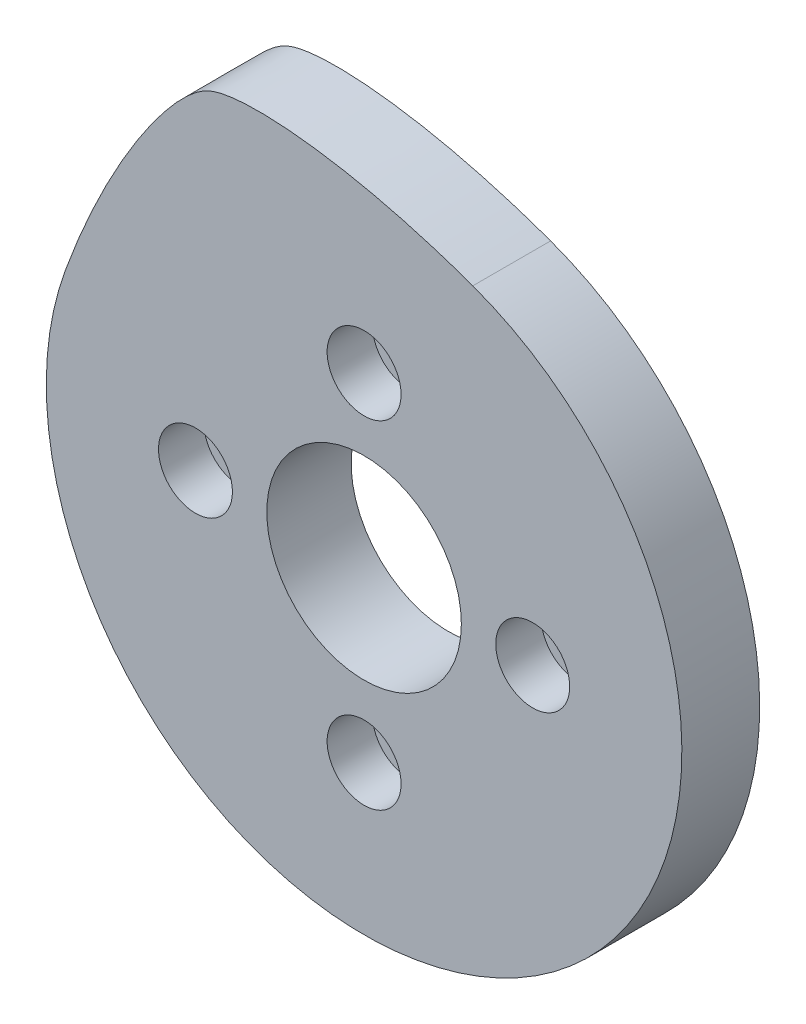
SolidWorks part; units mm, degrees
ref_plane "Front Plane" through (0, 0, 0) normal (1, 0, 0) x (0, 1, 0)
ref_plane "Top Plane" through (0, 0, 0) normal (0, 0, 1) x (0, 1, 0)
ref_plane "Right Plane" through (0, 0, 0) normal (0, 1, 0) x (-1, 0, 0)
sketch "Sketch1" plane through (0, 0, 0) normal (0, 0, 1) x (0, 1, 0)
  circle A0 centre (0, 0) radius 21
  circle A1 centre (0, 0) radius 13 construction
  circle A2 centre (0, 13) radius 1.6
  circle A3 centre (0, 13) radius 2.85
  circle A4 centre (13, 0) radius 2.85
  circle A5 centre (13, 0) radius 1.6
  circle A6 centre (0, -13) radius 2.85
  circle A7 centre (0, -13) radius 1.6
  circle A8 centre (-13, 0) radius 2.85
  circle A9 centre (-13, 0) radius 1.6
  point P19 (0, 0)
  dimension "D1" = 42
  dimension "D2" = 26
  dimension "D3" = 3.2
  dimension "D4" = 5.7
  dimension "D5" = 4
extrude "Boss-Extrude1" add sketch "Sketch1" along normal blind 6 contours A0 A8 A6 A4 A3 region at (0, 0, 0)
sketch "Sketch2" plane through (0, 0, 0) normal (0, 0, -1) x (1, 0, 0)
  line L0 (0, 0) -> (0, 28.5) construction
  line L1 (0, 0) -> (-12.0446, -25.8298) construction
  line L2 (0, 0) -> (-26.7812, -9.7476) construction
  line L3 (0, 0) -> (9.7476, -26.7812) construction
  line L4 (-13.7052, -25.0554) -> (-49.9575, -8.1507) construction
  line L5 (-8.9203, -47.1248) -> (-49.9627, 65.6383) construction
  line L6 (47.1248, -8.9203) -> (-65.6383, -49.9627) construction
  circle A0 centre (0, 0) radius 28.5 construction
  circle A1 centre (0, 0) radius 24.5
  spline S0 degree 3 poles (-23.0225, -8.3795) (-19.9443, -16.8367) (-14.7237, -24.6248) (-9.3995, -27.1075) (-0.0777, -26.1007) (8.3795, -23.0225) knots 0 0 0 0 0.45 0.55 1 1 1 1
  circle M5 centre (0, 0) radius 21
  dimension "D1" = 57
  dimension "D2" = 49
  dimension "D6" = 20
  dimension "D7" = 30
  dimension "D8" = 30
  dimension "D3" = 205
  dimension "D4" = 45
  dimension "D5" = 45
  dimension "D9" = 90
  dimension "D10" = 90
  dimension "D11" = 90
extrude "Boss-Extrude3" add sketch "Sketch2" against normal up to surface (6 mm away) contours A1 M5 | A1 S0 region at (19.5016, 13.6552, 0) region at (-10.6097, 22.7453, 0) up to face at (2.85, -13, 6)
extrude "Boss-Extrude2" add sketch "Sketch1<4>" along normal offset from surface (2.5 mm away) 3.5 contours A8 A9 | A3 A2 | A4 A5 | A6 A7 region at (-13, -2.7694, 0) region at (0, 10.2306, 0) region at (13, -2.7694, 0) region at (0, -15.7694, 0) up to face at (2.85, -13, 6)
sketch "Sketch1<4>" plane through (0, 0, 0) normal (0, 0, 1) x (0, 1, 0) same geometry as "Sketch1"
sketch "Sketch3" plane through (0, 0, 0) normal (0, 0, -1) x (1, 0, 0)
  circle A0 centre (0, 0) radius 21
  circle A1 centre (13, 0) radius 1.6
  circle A2 centre (0, 13) radius 1.6
  circle A3 centre (-13, 0) radius 1.6
  circle A4 centre (0, -13) radius 1.6
  dimension "D1" = 42
extrude "Boss-Extrude4" add sketch "Sketch3" along normal blind 0.5
sketch "Sketch4" plane through (0, 0, 6) normal (0, 0, 1) x (1, 0, 0)
  circle A0 centre (0, 0) radius 7.5
  dimension "D1" = 15
extrude "Cut-Extrude1" cut sketch "Sketch4" against normal through all contours A0
